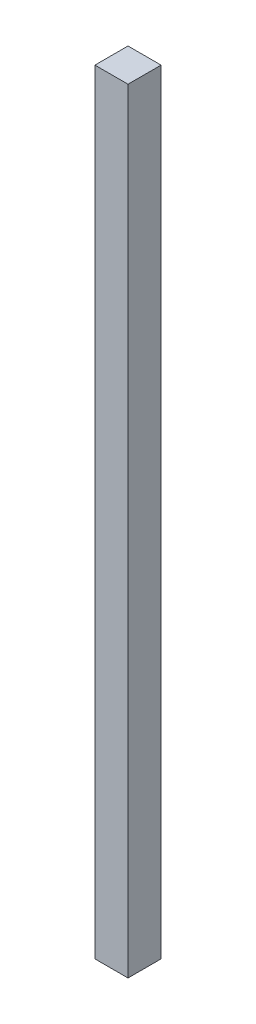
SolidWorks part; units mm, degrees
ref_plane "Front Plane" through (0, 0, 0) normal (0, 0, 1) x (1, 0, 0)
ref_plane "Top Plane" through (0, 0, 0) normal (0, 1, 0) x (1, 0, 0)
ref_plane "Right Plane" through (0, 0, 0) normal (1, 0, 0) x (0, 0, -1)
sketch "Sketch1" plane through (0, 0, 0) normal (0, 1, 0) x (1, 0, 0)
  line L1 (0, 0) -> (25.4, 0)
  line L2 (0, 0) -> (0, 25.4)
  line L3 (0, 25.4) -> (25.4, 25.4)
  line L4 (25.4, 0) -> (25.4, 25.4)
  dimension "D1" = 25.4
  dimension "D2" = 25.4
extrude "Boss-Extrude1" add sketch "Sketch1" along normal blind 609.6
sketch "Sketch3" plane through (0, 0, -25.4) normal (0, 0, -1) x (-1, 0, 0)
  line L0 (0, 609.6) -> (0, 0) construction
  line L1 (0, 484.0842) -> (-25.4, 484.0842)
  line L2 (0, 484.0842) -> (0, 609.6)
  line L3 (0, 609.6) -> (-25.4, 609.6)
  line L4 (-25.4, 484.0842) -> (-25.4, 609.6)
  line L5 (0, 484.0842) -> (-25.4, 484.0842) construction
extrude "Cut-Extrude1" [suppressed] cut sketch "Sketch3" against normal up to surface (25.4 mm away) up to face at (12.7, 304.8, 0)
sketch "Sketch4" [suppressed] plane through (0, 0, 0) normal (0, 0, 1) x (1, 0, 0)
  line L0 (0, 609.6) -> (0, 0) construction
  line L1 (0, 297.6179) -> (25.4, 297.6179)
  line L2 (0, 297.6179) -> (0, 609.6)
  line L3 (0, 609.6) -> (25.4, 609.6)
  line L4 (25.4, 297.6179) -> (25.4, 609.6)
  line L5 (25.4, 297.6179) -> (0, 297.6179) construction
extrude "Cut-Extrude2" [suppressed] cut sketch "Sketch4" against normal up to surface (25.4 mm away) up to face at (12.7, 304.8, -25.4)
sketch "Sketch5" plane through (0, 0, -25.4) normal (0, 0, -1) x (-1, 0, 0)
  line L0 (0, 609.6) -> (0, 0) construction
  line L1 (0, 594.2863) -> (-25.4, 594.2863)
  line L2 (0, 594.2863) -> (0, 609.6)
  line L3 (0, 609.6) -> (-25.4, 609.6)
  line L4 (-25.4, 594.2863) -> (-25.4, 609.6)
  line L5 (0, 594.2863) -> (-25.4, 594.2863) construction
extrude "Cut-Extrude3" cut sketch "Sketch5" against normal up to surface (25.4 mm away) up to face at (12.7, 304.8, 0)
sketch "Sketch6" [suppressed] plane through (0, 0, -25.4) normal (0, 0, -1) x (-1, 0, 0)
  line L0 (0, 609.6) -> (0, 0) construction
  line L1 (0, 574.651) -> (-25.4, 574.651)
  line L2 (0, 574.651) -> (0, 609.6)
  line L3 (0, 609.6) -> (-25.4, 609.6)
  line L4 (-25.4, 574.651) -> (-25.4, 609.6)
  line L5 (0, 574.651) -> (-25.4, 574.651) construction
extrude "Cut-Extrude4" [suppressed] cut sketch "Sketch6" against normal up to surface (25.4 mm away) up to face at (12.7, 297.1431, 0)
sketch "Sketch7" [suppressed] plane through (0, 0, 0) normal (0, 0, 1) x (1, 0, 0)
  line L0 (25.4, 609.6) -> (25.4, 0) construction
  line L1 (25.4, 443.1645) -> (0, 443.1645)
  line L2 (25.4, 443.1645) -> (25.4, 609.6)
  line L3 (25.4, 609.6) -> (0, 609.6)
  line L4 (0, 443.1645) -> (0, 609.6)
  line L5 (25.4, 443.1645) -> (0, 443.1645) construction
extrude "Cut-Extrude5" [suppressed] cut sketch "Sketch7" against normal up to surface (25.4 mm away) up to face at (12.7, 297.1431, -25.4)
sketch "Sketch8" [suppressed] plane through (0, 0, -25.4) normal (0, 0, -1) x (-1, 0, 0)
  line L0 (0, 609.6) -> (0, 0) construction
  line L1 (0, 340.2572) -> (-25.4, 340.2572)
  line L2 (0, 340.2572) -> (0, 609.6)
  line L3 (0, 609.6) -> (-25.4, 609.6)
  line L4 (-25.4, 340.2572) -> (-25.4, 609.6)
  line L5 (0, 340.2572) -> (-25.4, 340.2572) construction
extrude "Cut-Extrude6" [suppressed] cut sketch "Sketch8" against normal up to surface (25.4 mm away) up to face at (12.7, 297.1431, 0)
sketch "Sketch9" [suppressed] plane through (0, 0, 0) normal (0, 0, 1) x (1, 0, 0)
  line L0 (0, 609.6) -> (0, 0) construction
  line L1 (0, 350.8333) -> (25.4, 350.8333)
  line L2 (0, 350.8333) -> (0, 609.6)
  line L3 (0, 609.6) -> (25.4, 609.6)
  line L4 (25.4, 350.8333) -> (25.4, 609.6)
  line L5 (25.4, 350.8333) -> (0, 350.8333) construction
extrude "Cut-Extrude7" [suppressed] cut sketch "Sketch9" against normal up to surface (25.4 mm away) up to face at (12.7, 297.1431, -25.4)
